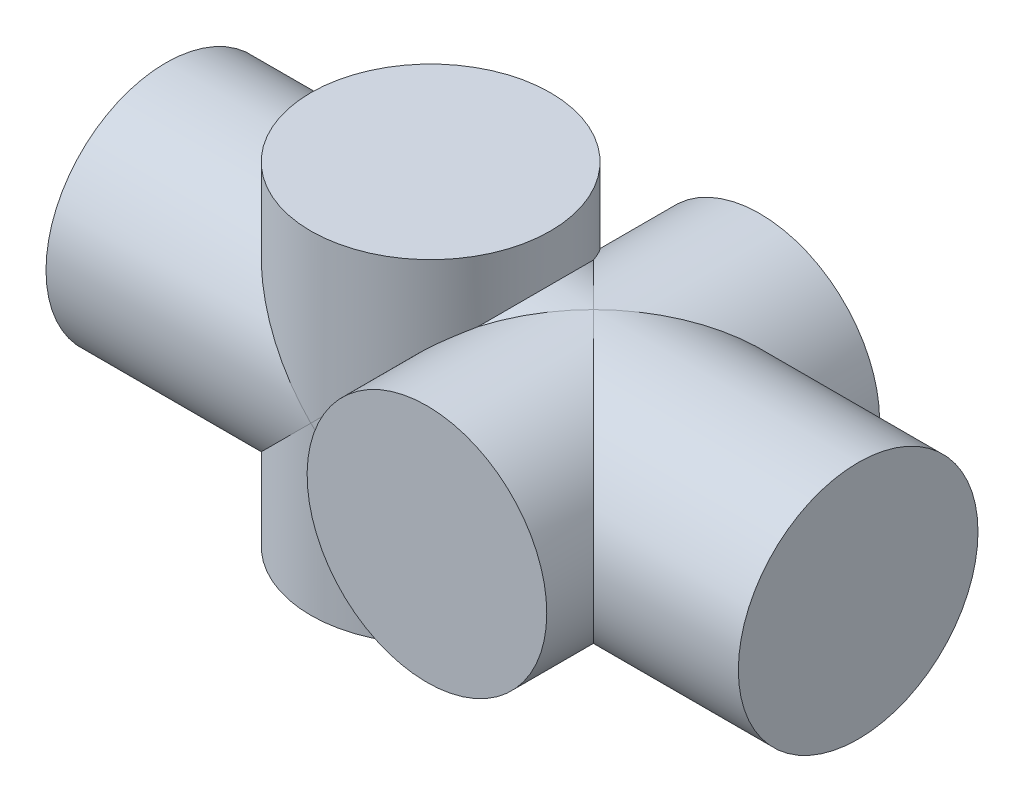
SolidWorks part; units mm, degrees
ref_plane "Alzado" through (0, 0, 0) normal (0, 0, 1) x (1, 0, 0)
ref_plane "Planta" through (0, 0, 0) normal (0, 1, 0) x (1, 0, 0)
ref_plane "Vista lateral" through (0, 0, 0) normal (1, 0, 0) x (0, 0, -1)
sketch "Croquis2" plane through (0, 0, 0) normal (0, 1, 0) x (1, 0, 0)
  line L0 (-310.5, 0) -> (157.5, 0) construction
  line L1 (-131.5, 83.75) -> (-131.5, -83.75) construction
  line L2 (-21.5, 137.75) -> (-21.5, -137.75) construction
  circle A0 centre (-131.5, 0) radius 81
  point P7 (-131.5, 0)
  point P8 (-21.5, 0)
  point P11 (-310.5, 0)
  dimension "D1" = 179
  dimension "D2" = 110
  dimension "D3" = 179
extrude "Saliente-Extruir1" add sketch "Croquis2" along normal mid plane 225
sketch "Croquis3" plane through (0, 0, 0) normal (0, 0, 1) x (1, 0, 0)
  line L0 (-131.5, -112.5) -> (-131.5, 112.5) construction
  line L5 (-212.5, -112.5) -> (-50.5, -112.5) construction
  line L6 (-50.5, 112.5) -> (-212.5, 112.5) construction
  line L7 (-21.5, 157.9645) -> (-21.5, -157.9645) construction
  line L8 (-310.5, 0) -> (157.5, 0) construction
  line L9 (-310.5, 0) -> (157.5, 0) construction
  circle A0 centre (-21.5, 0) radius 81
  point P13 (-21.5, 0)
  dimension "D1" = 110
extrude "Saliente-Extruir2" add sketch "Croquis3" along normal mid plane 225
sketch "Croquis5" plane through (0, 0, 0) normal (0, 0, 1) x (1, 0, 0)
  line L0 (-21.5, 81) -> (-21.5, -81) construction
  line L2 (157.5, 85.687) -> (157.5, -85.687) construction
  line L5 (-310.5, 0) -> (157.5, 0) construction
  circle A0 centre (-21.5, 0) radius 81 construction
  point P8 (157.5, 0)
  dimension "D1" = 179
sketch3d "Croquis3D7"
  line L2 (157.5, 85.687, 0) -> (157.5, -85.687, 0) construction
  circle A0 centre (157.5, 0, 0) radius 81
  point P2 (76.5, 0, 0)
extrude "Saliente-Extruir3" add sketch "Croquis3D7" along direction (1, 0, 0) on the side against the normal blind 468
